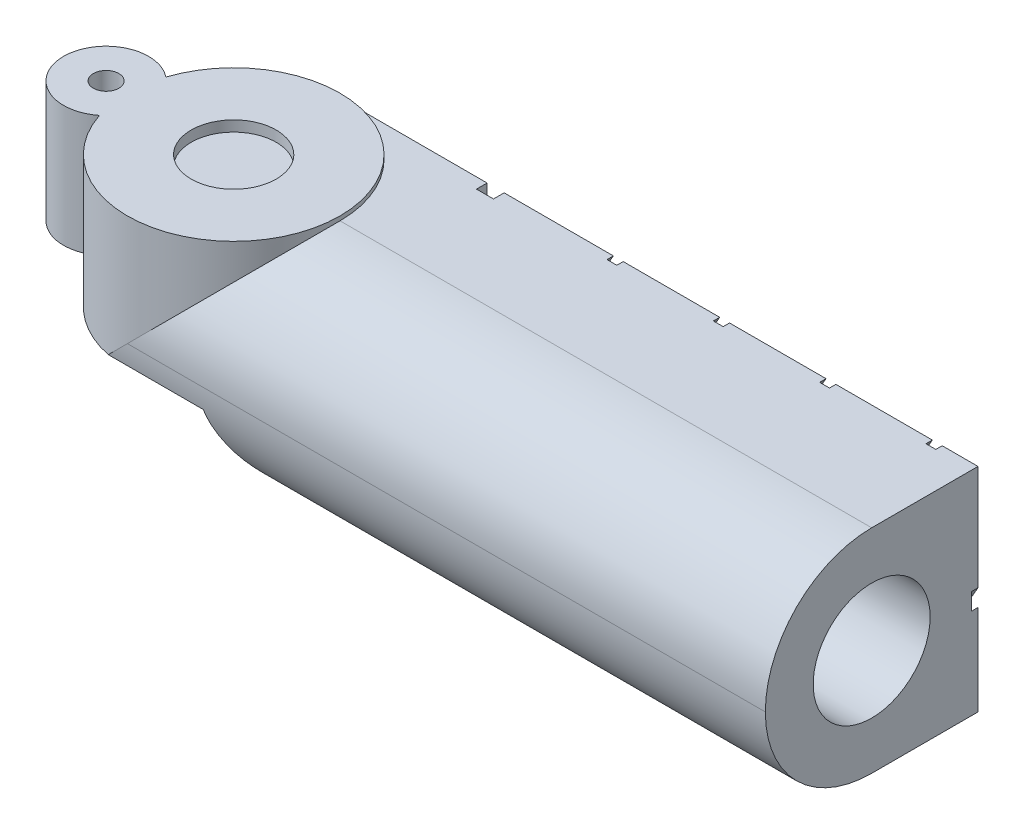
SolidWorks part; units mm, degrees
ref_plane "Front" through (0, 0, 0) normal (0, 0, 1) x (1, 0, 0)
ref_plane "Top" through (0, 0, 0) normal (0, 1, 0) x (1, 0, 0)
ref_plane "Right" through (0, 0, 0) normal (1, 0, 0) x (0, 0, -1)
sketch "草图1" plane through (0, 0, 0) normal (0, 1, 0) x (1, 0, 0)
  line L1 (17.5, -5) -> (-17.5, -5)
  line L2 (17.5, -5) -> (17.5, 5)
  line L3 (17.5, 5) -> (-17.5, 5)
  line L4 (-17.5, -5) -> (-17.5, 5)
  line L5 (17.5, -5) -> (-17.5, 5) construction
  line L6 (17.5, 5) -> (-17.5, -5) construction
  point P0 (0, 0)
  dimension "D1" = 10
  dimension "D2" = 35
extrude "凸台-拉伸1" add sketch "草图1" along normal blind 10
fillet "圆角1" radius 5 2 edges at (-17.5, 5, 5) (-17.5, 5, -5)
sketch "草图3" plane through (0, 0, 0) normal (0, -1, 0) x (1, 0, 0)
  line L0 (-12.5, -5) -> (-12.5, 11.1392) construction
  line L1 (6.6443, 0) -> (-22.4074, 0) construction
  circle A0 centre (-12.5, 0) radius 6
  dimension "D1" = 12
extrude "切除-拉伸1" cut sketch "草图3" against normal blind 4
sketch "草图6" plane through (0, 4, 0) normal (0, -1, 0) x (1, 0, 0)
  line L0 (-23.1563, 0) -> (6.017, 0) construction
  line L1 (-12.5, 8.9457) -> (-12.5, -8.0796) construction
  circle A0 centre (-12.5, 0) radius 1.25
  dimension "D1" = 2.5
sketch "草图7" plane through (0, 10, 0) normal (0, 1, 0) x (1, 0, 0)
  circle A0 centre (-12.5, 0) radius 5
extrude "凸台-拉伸4" add sketch "草图7" along normal blind 0.2
sketch "草图8" plane through (0, 10.2, 0) normal (0, 1, 0) x (1, 0, 0)
  circle A0 centre (-12.5, 0) radius 2
  dimension "D1" = 4
extrude "切除-拉伸3" cut sketch "草图8" against normal blind 0.5
fillet "圆角3" radius 5 2 edges at (4.1583, 0, 5) (2.5, 10, 5)
sketch "草图10" plane through (0, 10.2, 0) normal (0, 1, 0) x (1, 0, 0)
  line L0 (-8.4524, 0) -> (-22.2852, 0) construction
  line L1 (-12.5, 0) -> (-12.5, 8.6201) construction
  circle A0 centre (-18.5, 0) radius 2
  dimension "D1" = 4
  dimension "D2" = 6
extrude "凸台-拉伸5" add sketch "草图10" against normal blind 5.7
sketch "草图11" plane through (0, 10.2, 0) normal (0, 1, 0) x (1, 0, 0)
  line L0 (-12.5, 0) -> (-12.5, 8.0607) construction
  circle A0 centre (-18.5, 0) radius 0.6
  dimension "D1" = 1.2
  dimension "D2" = 6
extrude "切除-拉伸4" cut sketch "草图11" against normal through all
sketch "草图12" plane through (17.5, 0, 0) normal (1, 0, 0) x (0, 0, -1)
  line L0 (-5, 5) -> (9.6489, 5) construction
  circle A0 centre (0, 5) radius 2.75
  dimension "D1" = 5.5
extrude "切除-拉伸5" cut sketch "草图12" against normal blind 23
extrude "切除-拉伸6" cut sketch "草图6" against normal blind 4
fillet "圆角4" radius 1 1 edges at (-5.5, 5, -2.75)
sketch "草图13" plane through (0, 0, -5) normal (0, 0, -1) x (-1, 0, 0)
  line L6 (-17.5, 10) -> (12.5, 10) construction
  line L11 (5.5834, 0) -> (4.7834, 0)
  line L12 (5.5834, 0) -> (5.5834, 10)
  line L13 (5.5834, 10) -> (4.7834, 10)
  line L14 (4.7834, 0) -> (4.7834, 10)
  line L15 (5.5834, 0) -> (4.7834, 10) construction
  line L16 (5.5834, 10) -> (4.7834, 0) construction
  line L17 (-17.5, 0) -> (9.1834, 0) construction
  line L18 (9.1834, 0) -> (9.1834, 4) construction
  point P0 (5.1834, 5)
  dimension "D1" = 0.8
  dimension "D2" = 4
extrude "切除-拉伸7" cut sketch "草图13" against normal blind 0.5
sketch "草图14" plane through (0, 0, -5) normal (0, 0, -1) x (-1, 0, 0)
  line L0 (-17.5, 0) -> (1.1526, 10.7691) construction
  line L1 (-17.5, 0) -> (4.7834, 0) construction
  line L2 (-10.0311, -7.8805) -> (-20.5903, 10.4085)
  line L3 (-10.0311, -7.8805) -> (-10.3775, -8.0805)
  line L4 (-20.5903, 10.4085) -> (-20.9367, 10.2085)
  line L5 (-10.3775, -8.0805) -> (-20.9367, 10.2085)
  line L6 (-10.0311, -7.8805) -> (-20.9367, 10.2085) construction
  line L7 (-20.5903, 10.4085) -> (-10.3775, -8.0805) construction
  line L8 (-5.0311, -7.8805) -> (-15.5903, 10.4085)
  line L9 (-5.0311, -7.8805) -> (-5.3775, -8.0805)
  line L10 (-15.5903, 10.4085) -> (-15.9367, 10.2085)
  line L11 (-5.3775, -8.0805) -> (-15.9367, 10.2085)
  line L12 (-5.0311, -7.8805) -> (-15.9367, 10.2085) construction
  line L13 (-15.5903, 10.4085) -> (-5.3775, -8.0805) construction
  line L14 (-0.0311, -7.8805) -> (-10.5903, 10.4085)
  line L15 (-0.0311, -7.8805) -> (-0.3775, -8.0805)
  line L16 (-10.5903, 10.4085) -> (-10.9367, 10.2085)
  line L17 (-0.3775, -8.0805) -> (-10.9367, 10.2085)
  line L18 (-0.0311, -7.8805) -> (-10.9367, 10.2085) construction
  line L19 (-10.5903, 10.4085) -> (-0.3775, -8.0805) construction
  line L20 (4.9689, -7.8805) -> (-5.5903, 10.4085)
  line L21 (4.9689, -7.8805) -> (4.6225, -8.0805)
  line L22 (-5.5903, 10.4085) -> (-5.9367, 10.2085)
  line L23 (4.6225, -8.0805) -> (-5.9367, 10.2085)
  line L24 (4.9689, -7.8805) -> (-5.9367, 10.2085) construction
  line L25 (-5.5903, 10.4085) -> (4.6225, -8.0805) construction
  line L26 (9.9689, -7.8805) -> (-0.5903, 10.4085)
  line L27 (9.9689, -7.8805) -> (9.6225, -8.0805)
  line L28 (-0.5903, 10.4085) -> (-0.9367, 10.2085)
  line L29 (9.6225, -8.0805) -> (-0.9367, 10.2085)
  line L30 (9.9689, -7.8805) -> (-0.9367, 10.2085) construction
  line L31 (-0.5903, 10.4085) -> (9.6225, -8.0805) construction
  point P6 (-15.4839, 1.164)
  point P8 (-10.4839, 1.164)
  point P17 (-5.4839, 1.164)
  point P22 (-0.4839, 1.164)
  point P27 (4.5161, 1.164)
  dimension "D1" = 30
  dimension "D2" = 0.4
  dimension "D3" = 90
  dimension "D4" = 5
extrude "切除-拉伸8" cut sketch "草图14" against normal blind 0.3
